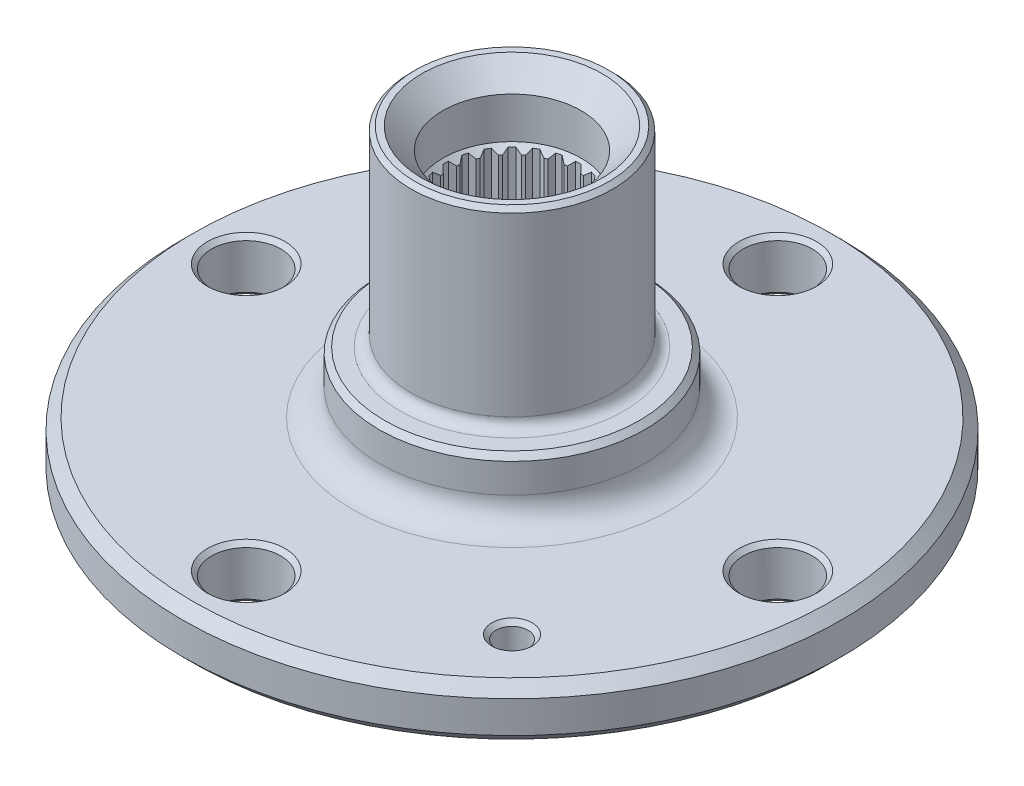
SolidWorks part; units mm, degrees
ref_plane "Plano frontal" through (0, 0, 0) normal (0, 0, 1) x (1, 0, 0)
ref_plane "Plano superior" through (0, 0, 0) normal (0, 1, 0) x (1, 0, 0)
ref_plane "Plano direito" through (0, 0, 0) normal (1, 0, 0) x (0, 0, -1)
sketch "Esboço1" plane through (0, 0, 0) normal (0, 0, 1) x (1, 0, 0)
  line L0 (0, -46.7425) -> (0, 47.9379) construction
  line L1 (13, 35.027) -> (11.75, 35.027)
  line L2 (11.75, 35.027) -> (11.75, -12.973)
  line L3 (11.75, -12.973) -> (24, -12.973)
  line L4 (24, -12.973) -> (24, -24.973)
  line L5 (24, -24.973) -> (27, -24.973)
  line L6 (27, -24.973) -> (27, -17.473)
  line L7 (27, -17.473) -> (31, -17.473)
  line L8 (31, -17.473) -> (31, -11.473)
  line L9 (31, -11.473) -> (62, -11.473)
  line L10 (62, -11.473) -> (62, -1.473)
  line L11 (62, -1.473) -> (25, -1.473)
  line L12 (25, -1.473) -> (25, 10.027)
  line L13 (25, 10.027) -> (19, 10.027)
  line L14 (19, 10.027) -> (19, 46.027)
  line L15 (19, 46.027) -> (13, 46.027)
  line L16 (13, 46.027) -> (13, 35.027)
  dimension "D1" = 11.75
  dimension "D2" = 13
  dimension "D3" = 19
  dimension "D4" = 36
  dimension "D5" = 25
  dimension "D6" = 62
  dimension "D7" = 11.5
  dimension "D8" = 10
  dimension "D9" = 13.5
  dimension "D10" = 6
  dimension "D11" = 11
  dimension "D12" = 24
  dimension "D13" = 31
  dimension "D14" = 27
  dimension "D15" = 12
revolve "Revolução1" add sketch "Esboço1" angle 360 about L0
sketch "Esboço2" plane through (0, -11.473, 0) normal (0, -1, 0) x (1, 0, 0)
  circle A0 centre (0, 0) radius 50 construction
  circle A1 centre (0, 50) radius 6.5
  circle A2 centre (-35.3553, -35.3553) radius 3
  circle A3 centre (50, 0) radius 6.5
  circle A4 centre (35.3553, 35.3553) radius 3
  circle A5 centre (0, -50) radius 6.5
  circle A7 centre (-50, 0) radius 6.5
  circle A9 centre (-35.3553, 35.3553) radius 6.5 [skipped]
  circle A10 centre (35.3553, -35.3553) radius 6.5 [skipped]
  circle A11 centre (35.3553, 35.3553) radius 6.5 [skipped]
  circle A12 centre (-35.3553, -35.3553) radius 6.5 [skipped]
  point P21 (0, 0)
  dimension "D1" = 100
  dimension "D2" = 13
  dimension "D4" = 6
  dimension "D5" = 6
  dimension "D3" = 8
extrude "Corte-extrusão1" cut sketch "Esboço2" against normal through all
chamfer "Chanfro2" distance 2 angle 45 1 edges at (0, 35.027, -11.75)
chamfer "Chanfro3" distance 1.5 angle 30 1 edges at (0, -12.973, -11.75) first distance on face at (0, -12.973, -24)
sketch "Esboço3" plane through (0, 35.027, 0) normal (0, 1, 0) x (1, 0, 0)
  line L0 (-0.5, 12.49) -> (-1.25, 11.6833)
  line L1 (0.5, 12.49) -> (1.25, 11.6833)
  line L2 (2.7497, 12.1938) -> (1.8165, 11.6087)
  line L3 (3.7156, 11.935) -> (4.2313, 10.9617)
  line L4 (5.812, 11.0667) -> (4.7591, 10.7431)
  line L5 (6.678, 10.5667) -> (6.9242, 9.4931)
  line L6 (8.4782, 9.1853) -> (7.3775, 9.1452)
  line L7 (9.1853, 8.4782) -> (9.1452, 7.3775)
  line L8 (10.5667, 6.678) -> (9.4931, 6.9242)
  line L9 (11.0667, 5.812) -> (10.7431, 4.7591)
  line L10 (11.935, 3.7156) -> (10.9617, 4.2313)
  line L11 (12.1938, 2.7497) -> (11.6087, 1.8165)
  line L12 (12.49, 0.5) -> (11.6833, 1.25)
  line L13 (12.49, -0.5) -> (11.6833, -1.25)
  line L14 (12.1938, -2.7497) -> (11.6087, -1.8165)
  line L15 (11.935, -3.7156) -> (10.9617, -4.2313)
  line L16 (11.0667, -5.812) -> (10.7431, -4.7591)
  line L17 (10.5667, -6.678) -> (9.4931, -6.9242)
  line L18 (9.1853, -8.4782) -> (9.1452, -7.3775)
  line L19 (8.4782, -9.1853) -> (7.3775, -9.1452)
  line L20 (6.678, -10.5667) -> (6.9242, -9.4931)
  line L21 (5.812, -11.0667) -> (4.7591, -10.7431)
  line L22 (3.7156, -11.935) -> (4.2313, -10.9617)
  line L23 (2.7497, -12.1938) -> (1.8165, -11.6087)
  line L24 (0.5, -12.49) -> (1.25, -11.6833)
  line L25 (-0.5, -12.49) -> (-1.25, -11.6833)
  line L26 (-2.7497, -12.1938) -> (-1.8165, -11.6087)
  line L27 (-3.7156, -11.935) -> (-4.2313, -10.9617)
  line L28 (-5.812, -11.0667) -> (-4.7591, -10.7431)
  line L29 (-6.678, -10.5667) -> (-6.9242, -9.4931)
  line L30 (-8.4782, -9.1853) -> (-7.3775, -9.1452)
  line L31 (-9.1853, -8.4782) -> (-9.1452, -7.3775)
  line L32 (-10.5667, -6.678) -> (-9.4931, -6.9242)
  line L33 (-11.0667, -5.812) -> (-10.7431, -4.7591)
  line L34 (-11.935, -3.7156) -> (-10.9617, -4.2313)
  line L35 (-12.1938, -2.7497) -> (-11.6087, -1.8165)
  line L36 (-12.49, -0.5) -> (-11.6833, -1.25)
  line L37 (-12.49, 0.5) -> (-11.6833, 1.25)
  line L38 (-12.1938, 2.7497) -> (-11.6087, 1.8165)
  line L39 (-11.935, 3.7156) -> (-10.9617, 4.2313)
  line L40 (-11.0667, 5.812) -> (-10.7431, 4.7591)
  line L41 (-10.5667, 6.678) -> (-9.4931, 6.9242)
  line L42 (-9.1853, 8.4782) -> (-9.1452, 7.3775)
  line L43 (-8.4782, 9.1853) -> (-7.3775, 9.1452)
  line L44 (-6.678, 10.5667) -> (-6.9242, 9.4931)
  line L45 (-5.812, 11.0667) -> (-4.7591, 10.7431)
  line L46 (-3.7156, 11.935) -> (-4.2313, 10.9617)
  line L47 (-2.7497, 12.1938) -> (-1.8165, 11.6087)
  arc A0 (2.7497, 12.1938) -> (3.7156, 11.935) centre (0, 0) cw
  arc A1 (-0.5, 12.49) -> (0.5, 12.49) centre (0, 0) cw
  arc A2 (-1.25, 11.6833) -> (1.25, 11.6833) centre (0, 0) cw
  arc A3 (1.8165, 11.6087) -> (4.2313, 10.9617) centre (0, 0) cw
  arc A4 (5.812, 11.0667) -> (6.678, 10.5667) centre (0, 0) cw
  arc A5 (4.7591, 10.7431) -> (6.9242, 9.4931) centre (0, 0) cw
  arc A6 (8.4782, 9.1853) -> (9.1853, 8.4782) centre (0, 0) cw
  arc A7 (7.3775, 9.1452) -> (9.1452, 7.3775) centre (0, 0) cw
  arc A8 (10.5667, 6.678) -> (11.0667, 5.812) centre (0, 0) cw
  arc A9 (9.4931, 6.9242) -> (10.7431, 4.7591) centre (0, 0) cw
  arc A10 (11.935, 3.7156) -> (12.1938, 2.7497) centre (0, 0) cw
  arc A11 (10.9617, 4.2313) -> (11.6087, 1.8165) centre (0, 0) cw
  arc A12 (12.49, 0.5) -> (12.49, -0.5) centre (0, 0) cw
  arc A13 (11.6833, 1.25) -> (11.6833, -1.25) centre (0, 0) cw
  arc A14 (12.1938, -2.7497) -> (11.935, -3.7156) centre (0, 0) cw
  arc A15 (11.6087, -1.8165) -> (10.9617, -4.2313) centre (0, 0) cw
  arc A16 (11.0667, -5.812) -> (10.5667, -6.678) centre (0, 0) cw
  arc A17 (10.7431, -4.7591) -> (9.4931, -6.9242) centre (0, 0) cw
  arc A18 (9.1853, -8.4782) -> (8.4782, -9.1853) centre (0, 0) cw
  arc A19 (9.1452, -7.3775) -> (7.3775, -9.1452) centre (0, 0) cw
  arc A20 (6.678, -10.5667) -> (5.812, -11.0667) centre (0, 0) cw
  arc A21 (6.9242, -9.4931) -> (4.7591, -10.7431) centre (0, 0) cw
  arc A22 (3.7156, -11.935) -> (2.7497, -12.1938) centre (0, 0) cw
  arc A23 (4.2313, -10.9617) -> (1.8165, -11.6087) centre (0, 0) cw
  arc A24 (0.5, -12.49) -> (-0.5, -12.49) centre (0, 0) cw
  arc A25 (1.25, -11.6833) -> (-1.25, -11.6833) centre (0, 0) cw
  arc A26 (-2.7497, -12.1938) -> (-3.7156, -11.935) centre (0, 0) cw
  arc A27 (-1.8165, -11.6087) -> (-4.2313, -10.9617) centre (0, 0) cw
  arc A28 (-5.812, -11.0667) -> (-6.678, -10.5667) centre (0, 0) cw
  arc A29 (-4.7591, -10.7431) -> (-6.9242, -9.4931) centre (0, 0) cw
  arc A30 (-8.4782, -9.1853) -> (-9.1853, -8.4782) centre (0, 0) cw
  arc A31 (-7.3775, -9.1452) -> (-9.1452, -7.3775) centre (0, 0) cw
  arc A32 (-10.5667, -6.678) -> (-11.0667, -5.812) centre (0, 0) cw
  arc A33 (-9.4931, -6.9242) -> (-10.7431, -4.7591) centre (0, 0) cw
  arc A34 (-11.935, -3.7156) -> (-12.1938, -2.7497) centre (0, 0) cw
  arc A35 (-10.9617, -4.2313) -> (-11.6087, -1.8165) centre (0, 0) cw
  arc A36 (-12.49, -0.5) -> (-12.49, 0.5) centre (0, 0) cw
  arc A37 (-11.6833, -1.25) -> (-11.6833, 1.25) centre (0, 0) cw
  arc A38 (-12.1938, 2.7497) -> (-11.935, 3.7156) centre (0, 0) cw
  arc A39 (-11.6087, 1.8165) -> (-10.9617, 4.2313) centre (0, 0) cw
  arc A40 (-11.0667, 5.812) -> (-10.5667, 6.678) centre (0, 0) cw
  arc A41 (-10.7431, 4.7591) -> (-9.4931, 6.9242) centre (0, 0) cw
  arc A42 (-9.1853, 8.4782) -> (-8.4782, 9.1853) centre (0, 0) cw
  arc A43 (-9.1452, 7.3775) -> (-7.3775, 9.1452) centre (0, 0) cw
  arc A44 (-6.678, 10.5667) -> (-5.812, 11.0667) centre (0, 0) cw
  arc A45 (-6.9242, 9.4931) -> (-4.7591, 10.7431) centre (0, 0) cw
  arc A46 (-3.7156, 11.935) -> (-2.7497, 12.1938) centre (0, 0) cw
  arc A47 (-4.2313, 10.9617) -> (-1.8165, 11.6087) centre (0, 0) cw
  point P100 (0, 0)
  dimension "D1" = 24
extrude "Corte-extrusão2" cut sketch "Esboço3" against normal through all
chamfer "Chanfro1" distance 4 angle 45 1 edges at (0, 46.027, -13)
chamfer "Chanfro4" distance 0.8 angle 45 1 edges at (0, 46.027, -19)
chamfer "Chanfro5" distance 2 angle 45 1 edges at (0, -1.473, -62)
fillet "Filete1" radius 2 1 edges at (0, 10.027, -19)
fillet "Filete2" radius 5 1 edges at (0, -1.473, -25)
chamfer "Chanfro6" distance 1 angle 45 1 edges at (0, 10.027, -25)
chamfer "Chanfro7" distance 0.8 angle 45 12 edges at (0, -11.473, -56.5) (0, -1.473, -43.5) (50, -11.473, -6.5) (50, -1.473, 6.5) (35.3553, -11.473, 32.3553) (35.3553, -1.473, 38.3553) (0, -11.473, 43.5) (0, -1.473, 56.5) (-50, -11.473, -6.5) (-50, -1.473, 6.5) (-35.3553, -11.473, -38.3553) (-35.3553, -1.473, -32.3553)
chamfer "Chanfro8" distance 2 angle 45 1 edges at (0, -11.473, -62)
fillet "Filete3" radius 1.5 1 edges at (0, -11.473, -31)
fillet "Filete4" radius 2 1 edges at (0, -17.473, -27)
chamfer "Chanfro9" distance 1 angle 45 1 edges at (0, -24.973, -24)
chamfer "Chanfro10" distance 0.5 angle 45 1 edges at (0, -24.973, -27)
fillet "Filete5" radius 1 1 edges at (0, -12.973, -24)
